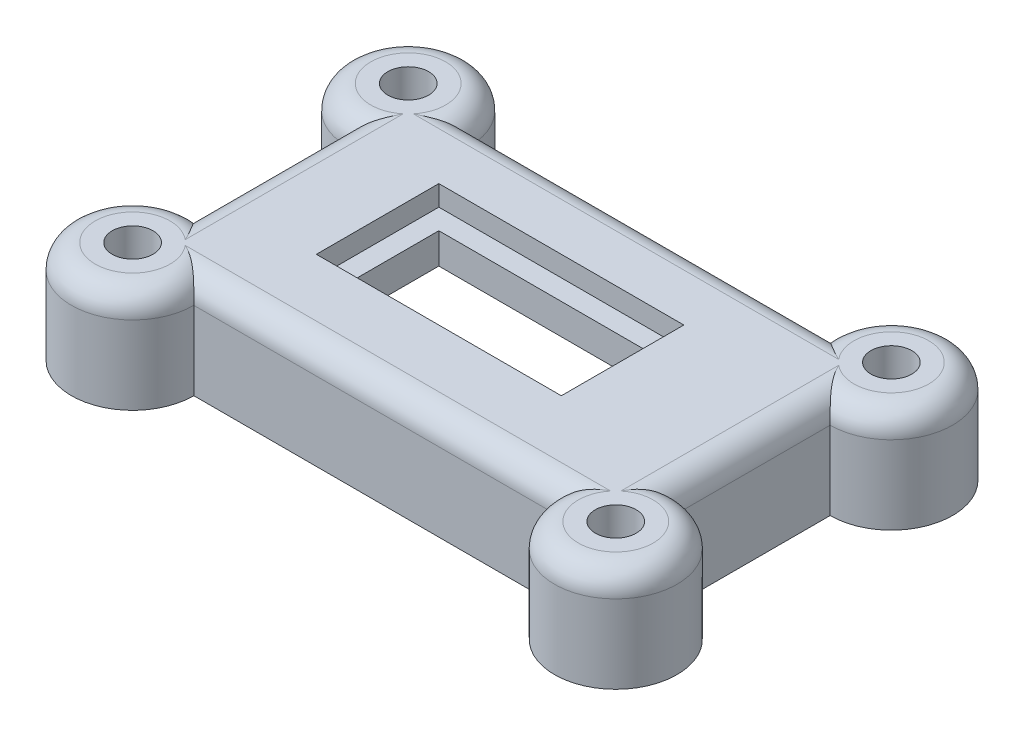
SolidWorks part; units mm, degrees
ref_plane "Front Plane" through (0, 0, 0) normal (0, 0, 1) x (1, 0, 0)
ref_plane "Top Plane" through (0, 0, 0) normal (0, 1, 0) x (1, 0, 0)
ref_plane "Right Plane" through (0, 0, 0) normal (1, 0, 0) x (0, 0, -1)
sketch "Sketch2" plane through (0, 0, 0) normal (0, 1, 0) x (1, 0, 0)
  line L0 (8, 35) -> (57.5, 35)
  line L1 (9, 0) -> (62, 0)
  line L2 (0, 9) -> (0, 31.5)
  line L3 (9, 40.5) -> (62, 40.5)
  line L4 (71, 9) -> (71, 31.5)
  line L5 (8, 5.5) -> (57.5, 5.5)
  line L6 (8, 5.5) -> (8, 35)
  line L7 (57.5, 35) -> (57.5, 5.5)
  arc A0 (9, 40.5) -> (0, 31.5) centre (0, 40.5) ccw
  arc A1 (0, 9) -> (9, 0) centre (0, 0) ccw
  arc A2 (71, 31.5) -> (62, 40.5) centre (71, 40.5) ccw
  arc A3 (62, 0) -> (71, 9) centre (71, 0) ccw
  dimension "D3" = 18
  dimension "D1" = 40.5
  dimension "D2" = 71
  dimension "D4" = 5.5
  dimension "D5" = 5.5
  dimension "D6" = 8
  dimension "D7" = 13.5
extrude "Boss-Extrude1" add sketch "Sketch2" along normal blind 15 contours L1 A3 L4 A2 L3 A0 L2 A1
extrude "Cut-Extrude1" cut sketch "Sketch2<4>" along normal blind 7.5 contours L5 L7 L0 L6
sketch "Sketch2<4>" plane through (0, 0, 0) normal (0, 1, 0) x (1, 0, 0) same geometry as "Sketch2"
sketch "Sketch3" plane through (0, 15, 0) normal (0, 1, 0) x (1, 0, 0)
  circle A0 centre (0, 0) radius 3
  circle A1 centre (0, 0) radius 1.85
  circle A2 centre (0, 40.5) radius 1.85
  circle A3 centre (71, 40.5) radius 1.85
  circle A4 centre (71, 0) radius 1.85
  circle A5 centre (0, 40.5) radius 3
  circle A6 centre (71, 40.5) radius 3
  circle A7 centre (71, 0) radius 3
  dimension "D1" = 3.7
  dimension "D2" = 6
extrude "Cut-Extrude2" cut sketch "Sketch3" against normal blind 6 contours A0 | A5 | A6 | A7
extrude "Cut-Extrude3" cut sketch "Sketch3<3>" against normal through all contours A1 | A2 | A3 | A4
sketch "Sketch3<3>" plane through (0, 15, 0) normal (0, 1, 0) x (1, 0, 0) same geometry as "Sketch3"
sketch "Sketch4" plane through (0, 15, 0) normal (0, 1, 0) x (1, 0, 0)
  line L0 (9, 40.5) -> (62, 40.5) construction
  line L1 (18, 15) -> (48, 15)
  line L2 (18, 15) -> (18, 27)
  line L3 (18, 27) -> (48, 27)
  line L4 (48, 15) -> (48, 27)
  line L6 (0, 9) -> (0, 31.5) construction
  line L7 (15, 12) -> (15, 30)
  line L8 (15, 30) -> (51, 30)
  line L9 (51, 12) -> (51, 30)
  line L10 (15, 12) -> (51, 12)
  dimension "D1" = 30
  dimension "D2" = 12
  dimension "D3" = 13.5
  dimension "D4" = 18
  dimension "D5" = 3
extrude "Cut-Extrude4" cut sketch "Sketch4" against normal up to surface (7.5 mm away) contours L1 L4 L3 L2 region at (33, 15, -21) up to face at (32.75, 7.5, -20.25)
extrude "Cut-Extrude5" cut sketch "Sketch4<3>" against normal blind 3
sketch "Sketch4<3>" plane through (0, 15, 0) normal (0, 1, 0) x (1, 0, 0) same geometry as "Sketch4"
fillet "Fillet2" radius 3.5 8 edges at (-6.364, 15, 6.364) (35.5, 15, 0) (77.364, 15, 6.364) (71, 15, -20.25) (77.364, 15, -46.864) (35.5, 15, -40.5) (-6.364, 15, -46.864) (0, 15, -20.25)
sketch "Sketch5" plane through (0, 0, 0) normal (0, -1, 0) x (1, 0, 0)
  line L0 (71, -40.5) -> (71, 0) construction
  line L1 (65, -7) -> (68, -7)
  line L2 (65, -7) -> (65, -37)
  line L3 (65, -37) -> (68, -37)
  line L4 (68, -7) -> (68, -37)
  line L5 (9, 0) -> (62, 0) construction
  dimension "D1" = 3
  dimension "D2" = 30
  dimension "D3" = 3
  dimension "D4" = 7
extrude "Cut-Extrude6" cut sketch "Sketch5" against normal blind 1.5
